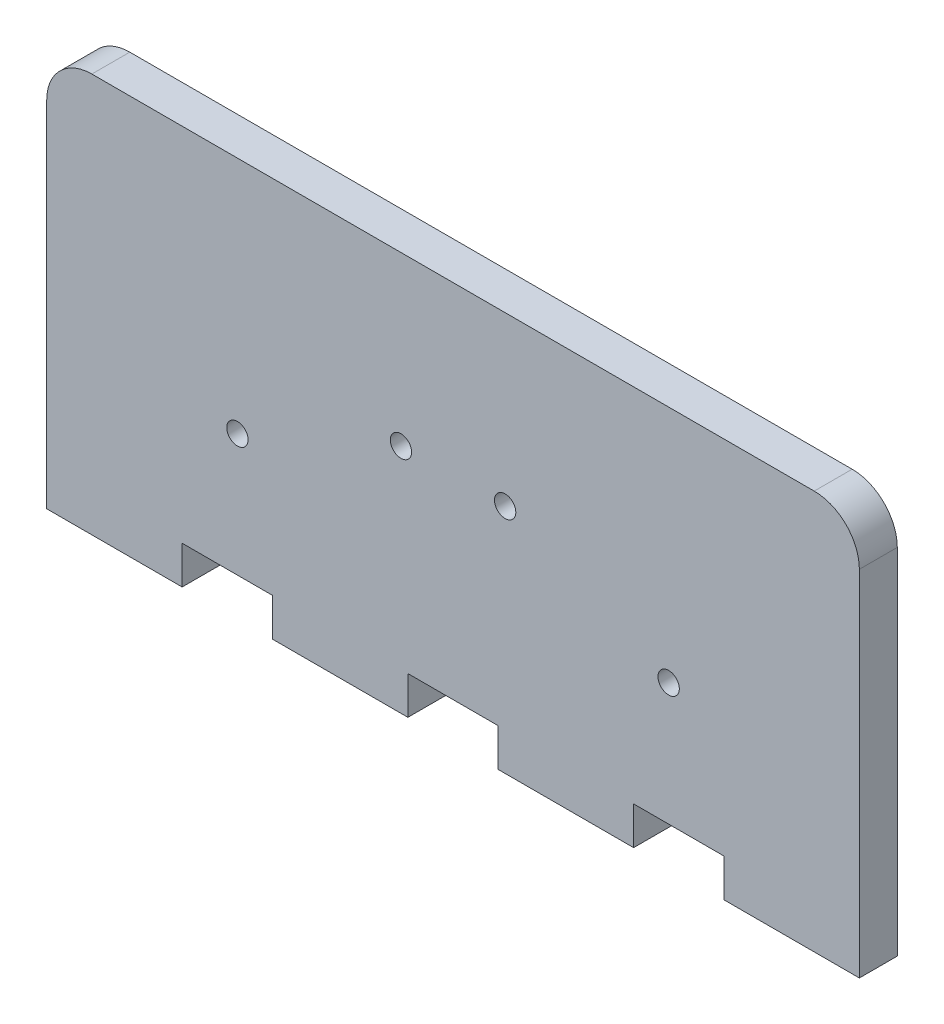
SolidWorks part; units mm, degrees
material "Teak"
ref_plane "Front Plane" through (0, 0, 0) normal (0, 0, 1) x (1, 0, 0)
ref_plane "Top Plane" through (0, 0, 0) normal (0, 1, 0) x (1, 0, 0)
ref_plane "Right Plane" through (0, 0, 0) normal (1, 0, 0) x (0, 0, -1)
sketch "Sketch1" plane through (0, 0, 0) normal (0, 0, 1) x (1, 0, 0)
  line L1 (-30.5325, 25.3111) -> (83.7675, 25.3111)
  line L2 (-30.5325, 25.3111) -> (-30.5325, -30.8229)
  line L3 (-30.5325, -30.8229) -> (83.7675, -30.8229)
  line L4 (83.7675, 25.3111) -> (83.7675, -30.8229)
  dimension "D1" = 56.134
  dimension "D2" = 114.3
extrude "Boss-Extrude1" add sketch "Sketch1" along normal blind 5.334 contours L1 L4 L3 L2
sketch "Sketch2" plane through (0, 0, 5.334) normal (0, 0, 1) x (1, 0, 0)
  line L0 (-30.5325, -30.8229) -> (83.7675, -30.8229) construction
  line L1 (-11.4825, -30.8229) -> (1.2175, -30.8229)
  line L2 (-11.4825, -30.8229) -> (-11.4825, -25.4889)
  line L3 (-11.4825, -25.4889) -> (1.2175, -25.4889)
  line L4 (1.2175, -30.8229) -> (1.2175, -25.4889)
  line L5 (-11.4825, -25.4889) -> (-30.5325, -25.4889) construction
  line L6 (20.2675, -30.8229) -> (32.9675, -30.8229)
  line L7 (20.2675, -30.8229) -> (20.2675, -25.4889)
  line L8 (20.2675, -25.4889) -> (32.9675, -25.4889)
  line L9 (32.9675, -30.8229) -> (32.9675, -25.4889)
  line L10 (52.0175, -30.8229) -> (64.7175, -30.8229)
  line L11 (52.0175, -30.8229) -> (52.0175, -25.4889)
  line L12 (52.0175, -25.4889) -> (64.7175, -25.4889)
  line L13 (64.7175, -30.8229) -> (64.7175, -25.4889)
  line L14 (-30.5325, 25.3111) -> (-30.5325, -30.8229) construction
  line L15 (1.2175, -25.4889) -> (20.2675, -25.4889) construction
  line L16 (32.9675, -25.4889) -> (52.0175, -25.4889) construction
  line L17 (64.7175, -25.4889) -> (83.7675, -25.4889) construction
  line L18 (83.7675, 25.3111) -> (83.7675, -30.8229) construction
  dimension "D1" = 19.05
  dimension "D2" = 12.7
  dimension "D3" = 19.05
  dimension "D4" = 12.7
  dimension "D5" = 19.05
  dimension "D6" = 12.7
  dimension "D7" = 19.05
  dimension "D8" = 5.334
extrude "Cut-Extrude1" cut sketch "Sketch2" against normal through all
fillet "Fillet1" radius 6.35 2 edges at (83.7675, 25.3111, 2.667) (-30.5325, 25.3111, 2.667)
sketch "Sketch3" plane through (0, 0, 0) normal (0, 0, -1) x (-1, 0, 0)
  line L16 (24.1825, 25.3111) -> (-77.4175, 25.3111)
  line L17 (-83.7675, 18.9611) -> (-83.7675, -30.8229)
  line L18 (-83.7675, -30.8229) -> (-64.7175, -30.8229)
  line L19 (-64.7175, -30.8229) -> (-64.7175, -25.4889)
  line L20 (-64.7175, -25.4889) -> (-52.0175, -25.4889)
  line L21 (-52.0175, -25.4889) -> (-52.0175, -30.8229)
  line L22 (-52.0175, -30.8229) -> (-32.9675, -30.8229)
  line L23 (-32.9675, -30.8229) -> (-32.9675, -25.4889)
  line L24 (-32.9675, -25.4889) -> (-20.2675, -25.4889)
  line L25 (-20.2675, -25.4889) -> (-20.2675, -30.8229)
  line L26 (-20.2675, -30.8229) -> (-1.2175, -30.8229)
  line L27 (-1.2175, -30.8229) -> (-1.2175, -25.4889)
  line L28 (-1.2175, -25.4889) -> (11.4825, -25.4889)
  line L29 (11.4825, -25.4889) -> (11.4825, -30.8229)
  line L30 (11.4825, -30.8229) -> (30.5325, -30.8229)
  line L31 (30.5325, -30.8229) -> (30.5325, 18.9611)
  line L32 (24.1825, 25.3111) -> (-77.4175, 25.3111)
  line L33 (-83.7675, 18.9611) -> (-83.7675, -30.8229)
  line L34 (-83.7675, -30.8229) -> (-64.7175, -30.8229)
  line L35 (-64.7175, -30.8229) -> (-64.7175, -25.4889)
  line L36 (-64.7175, -25.4889) -> (-52.0175, -25.4889)
  line L37 (-52.0175, -25.4889) -> (-52.0175, -30.8229)
  line L38 (-52.0175, -30.8229) -> (-32.9675, -30.8229)
  line L39 (-32.9675, -30.8229) -> (-32.9675, -25.4889)
  line L40 (-32.9675, -25.4889) -> (-20.2675, -25.4889)
  line L41 (-20.2675, -25.4889) -> (-20.2675, -30.8229)
  line L42 (-20.2675, -30.8229) -> (-1.2175, -30.8229)
  line L43 (-1.2175, -30.8229) -> (-1.2175, -25.4889)
  line L44 (-1.2175, -25.4889) -> (11.4825, -25.4889)
  line L45 (11.4825, -25.4889) -> (11.4825, -30.8229)
  line L46 (11.4825, -30.8229) -> (30.5325, -30.8229)
  line L47 (30.5325, -30.8229) -> (30.5325, 18.9611)
  line L48 (-83.7675, 18.9611) -> (-83.7675, -30.8229)
  line L49 (24.1825, 25.3111) -> (-77.4175, 25.3111)
  line L50 (30.5325, -30.8229) -> (30.5325, 18.9611)
  line L51 (11.4825, -30.8229) -> (30.5325, -30.8229)
  line L52 (11.4825, -25.4889) -> (11.4825, -30.8229)
  line L53 (-1.2175, -25.4889) -> (11.4825, -25.4889)
  line L54 (-1.2175, -30.8229) -> (-1.2175, -25.4889)
  line L55 (-20.2675, -30.8229) -> (-1.2175, -30.8229)
  line L56 (-20.2675, -25.4889) -> (-20.2675, -30.8229)
  line L57 (-32.9675, -25.4889) -> (-20.2675, -25.4889)
  line L58 (-32.9675, -30.8229) -> (-32.9675, -25.4889)
  line L59 (-52.0175, -30.8229) -> (-32.9675, -30.8229)
  line L60 (-52.0175, -25.4889) -> (-52.0175, -30.8229)
  line L61 (-64.7175, -25.4889) -> (-52.0175, -25.4889)
  line L62 (-64.7175, -30.8229) -> (-64.7175, -25.4889)
  line L63 (-83.7675, -30.8229) -> (-64.7175, -30.8229)
  line L64 (-83.7675, 18.9611) -> (-83.7675, -30.8229)
  line L65 (24.1825, 25.3111) -> (-77.4175, 25.3111)
  line L66 (30.5325, -30.8229) -> (30.5325, 18.9611)
  line L67 (11.4825, -30.8229) -> (30.5325, -30.8229)
  line L68 (11.4825, -25.4889) -> (11.4825, -30.8229)
  line L69 (-1.2175, -25.4889) -> (11.4825, -25.4889)
  line L70 (-1.2175, -30.8229) -> (-1.2175, -25.4889)
  line L71 (-20.2675, -30.8229) -> (-1.2175, -30.8229)
  line L72 (-20.2675, -25.4889) -> (-20.2675, -30.8229)
  line L73 (-32.9675, -25.4889) -> (-20.2675, -25.4889)
  line L74 (-32.9675, -30.8229) -> (-32.9675, -25.4889)
  line L75 (-52.0175, -30.8229) -> (-32.9675, -30.8229)
  line L76 (-52.0175, -25.4889) -> (-52.0175, -30.8229)
  line L77 (-64.7175, -25.4889) -> (-52.0175, -25.4889)
  line L78 (-64.7175, -30.8229) -> (-64.7175, -25.4889)
  line L79 (-83.7675, -30.8229) -> (-64.7175, -30.8229)
  circle A0 centre (3.7085, -8.2649) radius 1.5 construction
  circle A1 centre (-19.2915, 1.7351) radius 1.5 construction
  arc A2 (-77.4175, 25.3111) -> (-83.7675, 18.9611) centre (-77.4175, 18.9611) ccw
  arc A3 (30.5325, 18.9611) -> (24.1825, 25.3111) centre (24.1825, 18.9611) ccw
  arc A4 (-77.4175, 25.3111) -> (-83.7675, 18.9611) centre (-77.4175, 18.9611) ccw
  arc A5 (30.5325, 18.9611) -> (24.1825, 25.3111) centre (24.1825, 18.9611) ccw
  arc A6 (-77.4175, 25.3111) -> (-83.7675, 18.9611) centre (-77.4175, 18.9611) ccw
  arc A7 (30.5325, 18.9611) -> (24.1825, 25.3111) centre (24.1825, 18.9611) ccw
  arc A8 (-77.4175, 25.3111) -> (-83.7675, 18.9611) centre (-77.4175, 18.9611) ccw
  arc A9 (30.5325, 18.9611) -> (24.1825, 25.3111) centre (24.1825, 18.9611) ccw
  circle A10 centre (-56.9435, -8.2649) radius 1.5 construction
  circle A11 centre (-33.9435, 1.7351) radius 1.5 construction
  circle A12 centre (3.7085, -8.2649) radius 1.5
  circle A13 centre (-19.2915, 1.7351) radius 1.5
  circle A14 centre (-56.9435, -8.2649) radius 1.5
  circle A15 centre (-33.9435, 1.7351) radius 1.5
  dimension "D1" = 0
  dimension "D2" = 0
extrude "Cut-Extrude2" cut sketch "Sketch3" against normal through all contours A12 | A13 | A14 | A15
equation "\"MDF\"= .21in"
equation "\"Foamcore\"= .13in"
equation "\"Gmaterial\"= \"MDF\""
equation "\"D1@Sketch1\"=\"MDF\"+2"
equation "\"D1@Boss-Extrude1\"=\"MDF\""
equation "\"D8@Sketch2\"=\"MDF\""
